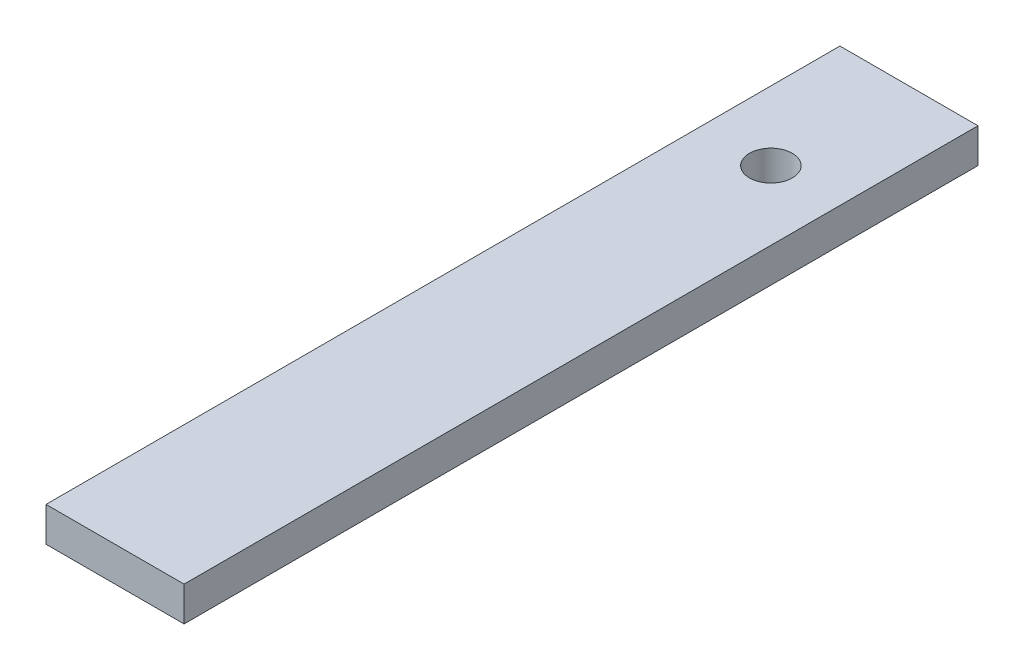
SolidWorks part; units mm, degrees
material "Maple"
ref_plane "Front Plane" through (0, 0, 0) normal (0, 0, 1) x (1, 0, 0)
ref_plane "Top Plane" through (0, 0, 0) normal (0, 1, 0) x (1, 0, 0)
ref_plane "Right Plane" through (0, 0, 0) normal (1, 0, 0) x (0, 0, -1)
sketch "Sketch1" plane through (0, 0, 0) normal (0, 1, 0) x (1, 0, 0)
  line L0 (0, 0) -> (50.8, 0)
  line L1 (0, 0) -> (0, 292.1)
  line L2 (50.8, 0) -> (50.8, 292.1)
  line L3 (0, 292.1) -> (50.8, 292.1)
  line L4 (25.4, 292.1) -> (25.4, 0) construction
  circle A0 centre (25.4, 241.3) radius 7.874
  dimension "D3" = 15.748
  dimension "D4" = 50.8
  dimension "D1" = 50.8
  dimension "D2" = 292.1
extrude "Boss-Extrude1" add sketch "Sketch1" along normal blind 12.7
ref_plane "Plane1" through (25.4, 0, 0) normal (-1, 0, 0) x (0, 0, 1)
